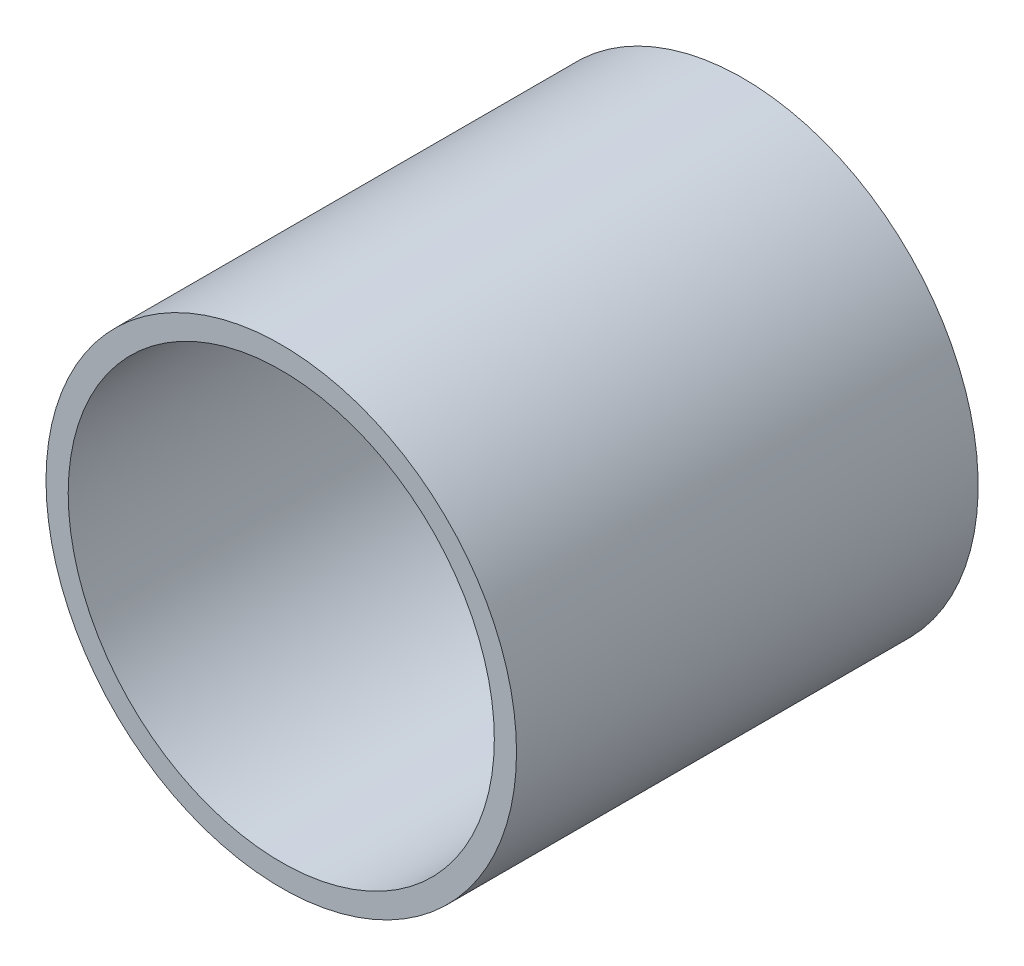
SolidWorks part; units mm, degrees
ref_plane "Front Plane" through (0, 0, 0) normal (1, 0, 0) x (0, 1, 0)
ref_plane "Top Plane" through (0, 0, 0) normal (0, 0, 1) x (0, 1, 0)
ref_plane "Right Plane" through (0, 0, 0) normal (0, 1, 0) x (-1, 0, 0)
ref_axis "x axis" through (-88.99, 0, 0) along (1, 0, 0)
ref_axis "y xxis" through (0, 88.99, 0) along (0, -1, 0)
ref_axis "z axis" through (0, 0, 55) along (0, 0, -1)
sketch "Sketch1" plane through (0, 0, 0) normal (0, 0, 1) x (0, 1, 0)
  circle A0 centre (0, 0) radius 24
  circle A1 centre (0, 0) radius 26.5
  dimension "D1" = 48
  dimension "D2" = 2.5
extrude "Boss-Extrude1" add sketch "Sketch1" along normal blind 50
sketch "Sketch2" plane through (0, 0, 0) normal (0, 0, -1) x (1, 0, 0)
  circle A0 centre (0, 0) radius 26.5
  circle A1 centre (0, 0) radius 26.5 construction
extrude "Boss-Extrude2" add sketch "Sketch2" along normal blind 2
sketch "Sketch5" plane through (0, 0, 0) normal (1, 0, 0) x (0, 1, 0)
  line L0 (-26.5, 0) -> (-26.5, 4.8)
  line L1 (-26.5, 50) -> (-26.5, -2) construction
  line L2 (-26.5, 4.8) -> (-19.5, 4.8)
  line L4 (-17, 0) -> (-26.5, 0)
  line L5 (0, 0) -> (0, 4.8) construction
  line L7 (24, 0) -> (-24, 0) construction
  spline S0 degree 2 poles (-19.5, 4.8) (-19.1439, 1.9411) (-17, 0) knots 0 0 0 1 1 1
  point P10 (-18.7361, 2.2468)
  dimension "D1" = 4.8
  dimension "D2" = 19.5
  dimension "D3" = 17
revolve "Revolve1" add sketch "Sketch5" angle 360 about L5
